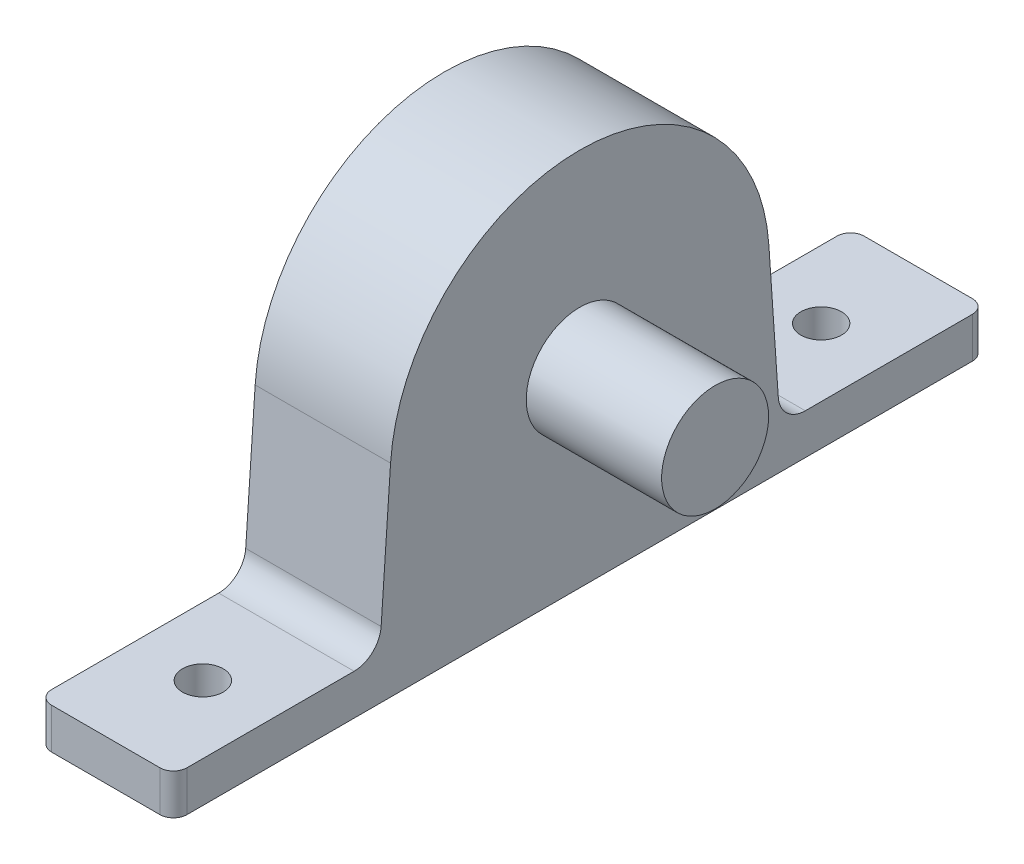
SolidWorks part; units mm, degrees
ref_plane "Front Plane" through (0, 0, 0) normal (0, 0, 1) x (1, 0, 0)
ref_plane "Top Plane" through (0, 0, 0) normal (0, 1, 0) x (1, 0, 0)
ref_plane "Right Plane" through (0, 0, 0) normal (1, 0, 0) x (0, 0, -1)
sketch "Sketch1" plane through (0, 0, 0) normal (1, 0, 0) x (0, 0, -1)
  line L0 (-15, 0) -> (15, 0)
  line L1 (-15, 0) -> (-9.5209, 17.0581)
  line L2 (9.5209, 17.0581) -> (15, 0)
  line L3 (0, 3) -> (-11, 3) construction
  line L4 (0, 25) -> (9.5209, 25) construction
  line L5 (0, 28) -> (15, 28) construction
  line L6 (-15, 0) -> (-13.5737, 20.6565) construction
  line L7 (0, 14) -> (0, 0) construction
  line L8 (15, 0) -> (13.5737, 20.6565) construction
  arc A0 (-9.5209, 17.0581) -> (9.5209, 17.0581) centre (0, 14) cw
  circle A1 centre (0, 14) radius 11 construction
  arc A2 (-12.5173, 7.7296) -> (13.1196, 9.1136) centre (0, 14) ccw construction
  arc A3 (13.9667, 14.9644) -> (-13.9667, 14.9644) centre (0, 14) ccw construction
  point P4 (0, 0)
  point P15 (7.5, 28)
  dimension "D2" = 10
  dimension "D4" = 22
  dimension "D1" = 30
  dimension "D3" = 14
  dimension "D5" = 3
extrude "Boss-Extrude1" add sketch "Sketch1" along normal blind 10
sketch "Sketch2" plane through (10, 0, 0) normal (1, 0, 0) x (0, 0, -1)
  circle A0 centre (0, 14) radius 3.95
  dimension "D1" = 7.9
extrude "Boss-Extrude2" add sketch "Sketch2" along normal blind 10
sketch "Sketch4" plane through (10, 0, 0) normal (1, 0, 0) x (0, 0, -1)
  line L0 (15, 0) -> (13.5737, 20.6565) construction
  line L1 (-15, 0) -> (-13.5737, 20.6565) construction
  line L2 (15, 0) -> (13.5737, 20.6565)
  line L3 (-15, 0) -> (15, 0)
  line L4 (15, 0) -> (9.5209, 17.0581)
  line L5 (-9.5209, 17.0581) -> (-15, 0)
  line L6 (-15, 0) -> (15, 0)
  line L7 (15, 0) -> (9.5209, 17.0581)
  line L8 (-9.5209, 17.0581) -> (-15, 0)
  line L9 (-15, 0) -> (-13.5737, 20.6565)
  arc A0 (13.9667, 14.9644) -> (-13.9667, 14.9644) centre (0, 14) ccw construction
  arc A1 (9.5209, 17.0581) -> (-9.5209, 17.0581) centre (0, 14) ccw
  arc A2 (9.5209, 17.0581) -> (-9.5209, 17.0581) centre (0, 14) ccw
  arc A3 (13.9667, 14.9644) -> (-13.9667, 14.9644) centre (0, 14) ccw
  arc M6 (9.5209, 17.0581) -> (-9.5209, 17.0581) centre (0, 14) ccw
  line M7 (-9.5209, 17.0581) -> (-15, 0)
  line M9 (15, 0) -> (9.5209, 17.0581)
  dimension "D1" = 0
extrude "Boss-Extrude3" add sketch "Sketch4" against normal up to surface (10 mm away) contours L2 A3 L9 M7 M6 M9 region at (10, 8.6546, -12.6512) up to face at (0, 10.2645, 0)
sketch "Sketch5" plane through (0, 0, 0) normal (0, -1, 0) x (1, 0, 0)
  line L0 (10, 15) -> (10, -15) construction
  line L1 (0, 30) -> (10, 30)
  line L2 (0, 30) -> (0, -30)
  line L3 (0, -30) -> (10, -30)
  line L4 (10, 30) -> (10, -30)
  line L5 (0, 15) -> (0, -15) construction
  point P9 (0, 0)
  dimension "D1" = 60
extrude "Boss-Extrude4" add sketch "Sketch5" against normal blind 3
fillet "Fillet1" radius 1 4 edges at (0, 1.5, -30) (0, 1.5, 30) (10, 1.5, 30) (10, 1.5, -30)
fillet "Fillet2" radius 2 2 edges at (5, 3, -14.7929) (5, 3, 14.7929)
sketch "Sketch7" plane through (0, 3, 0) normal (0, 1, 0) x (1, 0, 0)
  line L0 (1, 30) -> (9, 30) construction
  line L1 (0, -29) -> (0, -16.6595) construction
  line L2 (0, 16.6595) -> (0, 29) construction
  circle A0 centre (5, 22.8298) radius 1.5
  circle A1 centre (5, -22.8298) radius 1.5
  point P6 (5, 30)
  point P9 (0, -22.8298)
  point P12 (0, 22.8298)
  dimension "D1" = 3
extrude "Cut-Extrude1" cut sketch "Sketch7" against normal blind 3
